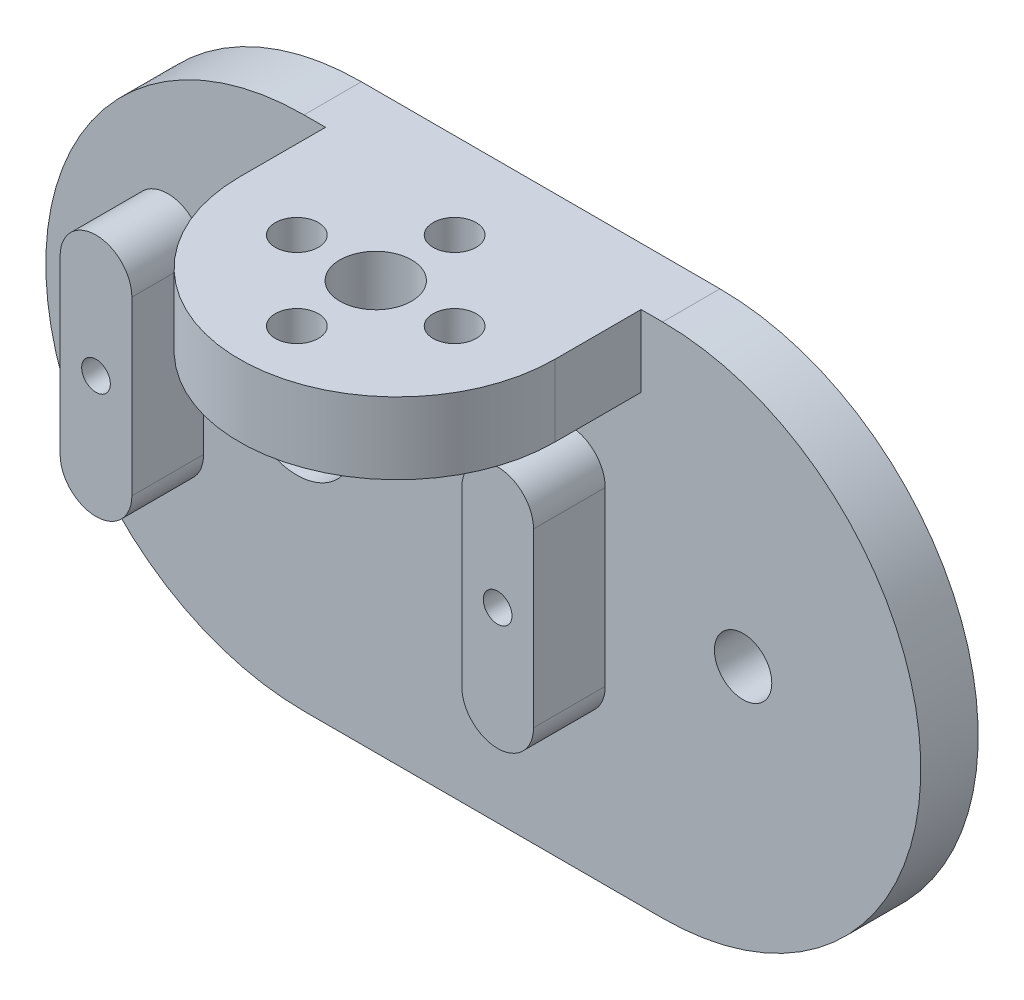
SolidWorks part; units mm, degrees
ref_plane "Front Plane" through (0, 0, 0) normal (0, 0, 1) x (1, 0, 0)
ref_plane "Top Plane" through (0, 0, 0) normal (0, 1, 0) x (1, 0, 0)
ref_plane "Right Plane" through (0, 0, 0) normal (1, 0, 0) x (0, 0, -1)
sketch "Sketch1" plane through (0, 0, 0) normal (0, 0, 1) x (1, 0, 0)
  line L0 (0, 0) -> (0, 16954.6425) construction
  line L1 (0, 0) -> (-16954.6425, 0) construction
  line L2 (-12.5, 0) -> (12.5, 0) construction
  line L3 (-12.5, 18) -> (12.5, 18)
  line L4 (-12.5, -18) -> (12.5, -18)
  arc A0 (-12.5, 18) -> (-12.5, -18) centre (-12.5, 0) ccw
  arc A1 (12.5, -18) -> (12.5, 18) centre (12.5, 0) ccw
  point P7 (0, 0)
  point P12 (0, 0)
  dimension "D1" = 18
  dimension "D2" = 25
extrude "Boss-Extrude1" add sketch "Sketch1" along normal blind 4
sketch "Sketch2" plane through (0, 0, 4) normal (0, 0, 1) x (1, 0, 0)
  line L0 (0, 0) -> (0, 50000) construction
  line L1 (0, 0) -> (-50000, 0) construction
  line L2 (6, 6) -> (6, -6) construction
  line L3 (8.5, 6) -> (8.5, -6)
  line L4 (3.5, 6) -> (3.5, -6)
  line L5 (-22, 6) -> (-22, -6) construction
  line L6 (-19.5, 6) -> (-19.5, -6)
  line L7 (-24.5, 6) -> (-24.5, -6)
  arc A0 (8.5, 6) -> (3.5, 6) centre (6, 6) ccw
  arc A1 (3.5, -6) -> (8.5, -6) centre (6, -6) ccw
  arc A2 (-19.5, 6) -> (-24.5, 6) centre (-22, 6) ccw
  arc A3 (-24.5, -6) -> (-19.5, -6) centre (-22, -6) ccw
  circle A5 centre (-13, 0) radius 4
  circle A6 centre (-22, 0) radius 1
  circle A7 centre (6, 0) radius 1
  circle A8 centre (18.1102, 0) radius 2
  point P7 (6, 0)
  point P12 (-22, 0)
  dimension "D2" = 2.5
  dimension "D4" = 2.5
  dimension "D6" = 28
  dimension "D7" = 2
  dimension "D8" = 8
  dimension "D10" = 4
  dimension "D1" = 12
  dimension "D3" = 12
  dimension "D5" = 22
  dimension "D9" = 9
extrude "Boss-Extrude2" add sketch "Sketch2" along normal blind 5 contours L7 A3 L6 A2 A6 | L4 A1 L3 A0 A7 region at (8.3228, 0, 4) region at (-19.6772, 0, 4)
extrude "Cut-Extrude1" cut sketch "Sketch2<3>" against normal blind 5 contours A5 | A8 | A6 | A7 region at (-13, 0, 4) region at (-22, 0, 4) region at (6, 0, 4) region at (18.1102, 0, 4)
sketch "Sketch2<3>" plane through (0, 0, 4) normal (0, 0, 1) x (1, 0, 0) same geometry as "Sketch2"
sketch "Sketch3" plane through (0, 0, 4) normal (0, 0, 1) x (1, 0, 0)
  line L0 (0, 0) -> (0, -50000) construction
  line L1 (11, 18) -> (-11, 18)
  line L2 (11, 18) -> (11, 13)
  line L3 (11, 13) -> (-11, 13)
  line L4 (-11, 18) -> (-11, 13)
  dimension "D1" = 22
  dimension "D2" = 5
extrude "Boss-Extrude3" add sketch "Sketch3" along normal blind 17
fillet "Fillet1" 2 edges at (-11, 15.5, 21) (11, 15.5, 21) type full round first side face at (-11, 15.5, 12.5) second side face at (11, 15.5, 12.5) middle face at (0, 15.5, 21)
sketch "Sketch5" plane through (0, 13, 0) normal (0, -1, 0) x (1, 0, 0)
  circle A0 centre (0, 11.5) radius 5.5
  circle A1 centre (0, 11.5) radius 2.5
  circle A6 centre (5.5, 11.5) radius 1.5
  circle A7 centre (0, 17) radius 1.5
  circle A8 centre (-5.5, 11.5) radius 1.5
  circle A9 centre (0, 6) radius 1.5
  dimension "D1" = 11
  dimension "D2" = 5
  dimension "D3" = 3
  dimension "D5" = 11.5
extrude "Cut-Extrude3" cut sketch "Sketch5" against normal blind 17 contours A0 A6 | A0 A6 | A0 A7 | A0 A7 | A1 | A0 A8 | A0 A8 | A0 A9 | A0 A9 region at (4.828, 13, 11.5) region at (6.0984, 13, 11.5) region at (0, 13, 16.328) region at (0, 13, 17.5984) region at (0, 13, 5.4016) region at (0, 13, 6.672) region at (-4.828, 13, 11.5) region at (-6.0984, 13, 11.5) region at (0, 13, 11.5)
